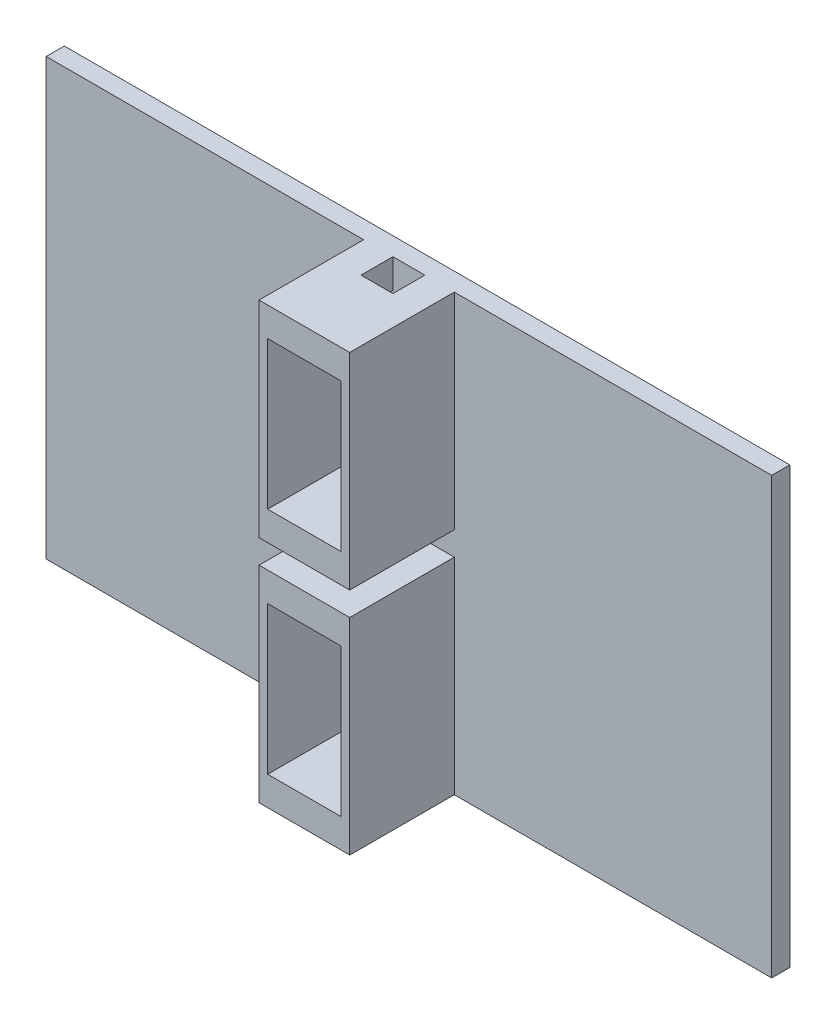
SolidWorks part; units mm, degrees
ref_plane "Front Plane" through (0, 0, 0) normal (0, 0, 1) x (1, 0, 0)
ref_plane "Top Plane" through (0, 0, 0) normal (0, 1, 0) x (1, 0, 0)
ref_plane "Right Plane" through (0, 0, 0) normal (1, 0, 0) x (0, 0, -1)
sketch "Sketch1" plane through (0, 0, 0) normal (0, 0, 1) x (1, 0, 0)
  line L1 (-100, 60) -> (100, 60)
  line L2 (-100, 60) -> (-100, -60)
  line L3 (-100, -60) -> (100, -60)
  line L4 (100, 60) -> (100, -60)
  line L5 (-100, 60) -> (100, -60) construction
  line L6 (-100, -60) -> (100, 60) construction
  point P0 (0, 0)
  dimension "D1" = 200
  dimension "D2" = 120
extrude "Boss-Extrude1" add sketch "Sketch1" along normal blind 5
sketch "Sketch2" plane through (0, 0, 5) normal (0, 0, 1) x (1, 0, 0)
  line L0 (0, 3.28) -> (0, -60)
  line L9 (60, 60) -> (60, -60)
  line L10 (-60, 60) -> (-60, -60)
  line L12 (100, 60) -> (-100, 60) construction
  line L13 (12.5, 60) -> (12.5, 3.28)
  line L14 (-12.5, 60) -> (-12.5, 3.28)
  line L15 (-12.5, 3.28) -> (12.5, 3.28)
  line L16 (0, 60) -> (0, -60) construction
  line L17 (-12.5, 60) -> (12.5, 60)
  line M17 (100, 60) -> (-100, 60)
extrude "Boss-Extrude2" add sketch "Sketch2" along normal blind 28.82 contours L16 L17 L14 L15 | L16 L15 L13 M17 region at (6.25, 31.64, 5) region at (-6.25, 31.64, 5)
sketch "Sketch3" plane through (0, 0, 33.82) normal (0, 0, 1) x (1, 0, 0)
  line L2 (-10.11, 52) -> (10.11, 52)
  line L3 (10.11, 52) -> (10.11, 11.28)
  line L4 (-10.11, 52) -> (-10.11, 11.28)
  line L5 (10.11, 11.28) -> (-10.11, 11.28)
extrude "Cut-Extrude1" cut sketch "Sketch3" against normal blind 28.82
sketch "Sketch4" plane through (0, 52, 0) normal (0, -1, 0) x (1, 0, 0)
  line L0 (-4.4, 5) -> (4.4, 5)
  line L1 (10.11, 5) -> (-10.11, 5) construction
  line L2 (-4.4, 5) -> (-4.4, 13.8)
  line L3 (-4.4, 13.8) -> (4.4, 13.8)
  line L4 (4.4, 13.8) -> (4.4, 5)
extrude "Cut-Extrude2" cut sketch "Sketch4" against normal blind 19.82
ref_plane "Plane1" through (0, 0, 0) normal (0, 1, 0) x (1, 0, 0)
mirror "Mirror1" about plane through (0, 0, 0) normal (0, 1, 0) of "Cut-Extrude1", "Boss-Extrude1", "Boss-Extrude2"
sketch "Sketch5" plane through (0, -52, 0) normal (0, 1, 0) x (1, 0, 0)
  line L0 (-4.4, -5) -> (4.4, -5) construction
  line L1 (4.4, -5) -> (4.4, -13.8) construction
  line L2 (4.4, -13.8) -> (-4.4, -13.8) construction
  line L3 (-4.4, -13.8) -> (-4.4, -5) construction
  line L4 (-4.4, -5) -> (4.4, -5)
  line L5 (4.4, -5) -> (4.4, -13.8)
  line L6 (4.4, -13.8) -> (-4.4, -13.8)
  line L7 (-4.4, -13.8) -> (-4.4, -5)
extrude "Cut-Extrude3" cut sketch "Sketch5" against normal blind 19.82
